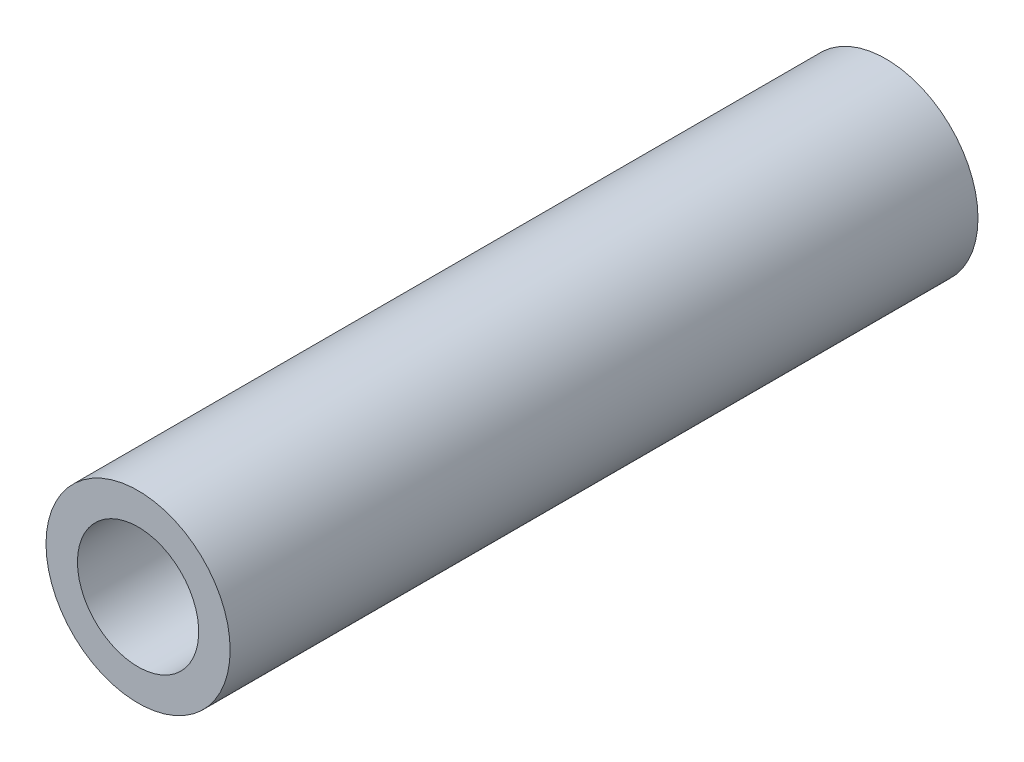
SolidWorks part; units mm, degrees
ref_plane "Front Plane" through (0, 0, 0) normal (0, 0, 1) x (1, 0, 0)
ref_plane "Top Plane" through (0, 0, 0) normal (0, 1, 0) x (1, 0, 0)
ref_plane "Right Plane" through (0, 0, 0) normal (1, 0, 0) x (0, 0, -1)
sketch "Sketch1" plane through (0, 0, 0) normal (0, 0, 1) x (1, 0, 0)
  circle A3 centre (59.4755, 35.57) radius 4.1
extrude "Boss-Extrude2" add sketch "Sketch1" along normal up to surface (33.3 mm away)
hole_wizard "M5 Clearance Hole1" positions "Sketch2" profile "Sketch3" hole size "M5" standard "ISO" end condition through all
sketch "Sketch2" plane through (0, 0, 0) normal (0, 0, -1) x (-1, 0, 0)
  point P0 (-59.4755, 35.57)
sketch "Sketch3" plane through (59.4755, 35.57, 0) normal (1, 0, 0) x (0, 1, 0)
  line L0 (0, 0) -> (0, 33.3)
  line L1 (0, 33.3) -> (2.7, 33.3)
  line L2 (2.7, 33.3) -> (2.7, 0)
  line L5 (2.7, 0) -> (0, 0)
  line L11 (0, -6.35) -> (0, 107.95) construction
  dimension "Thru Hole Dia." = 5.4
  dimension "Thru Hole Depth" = 33.3
